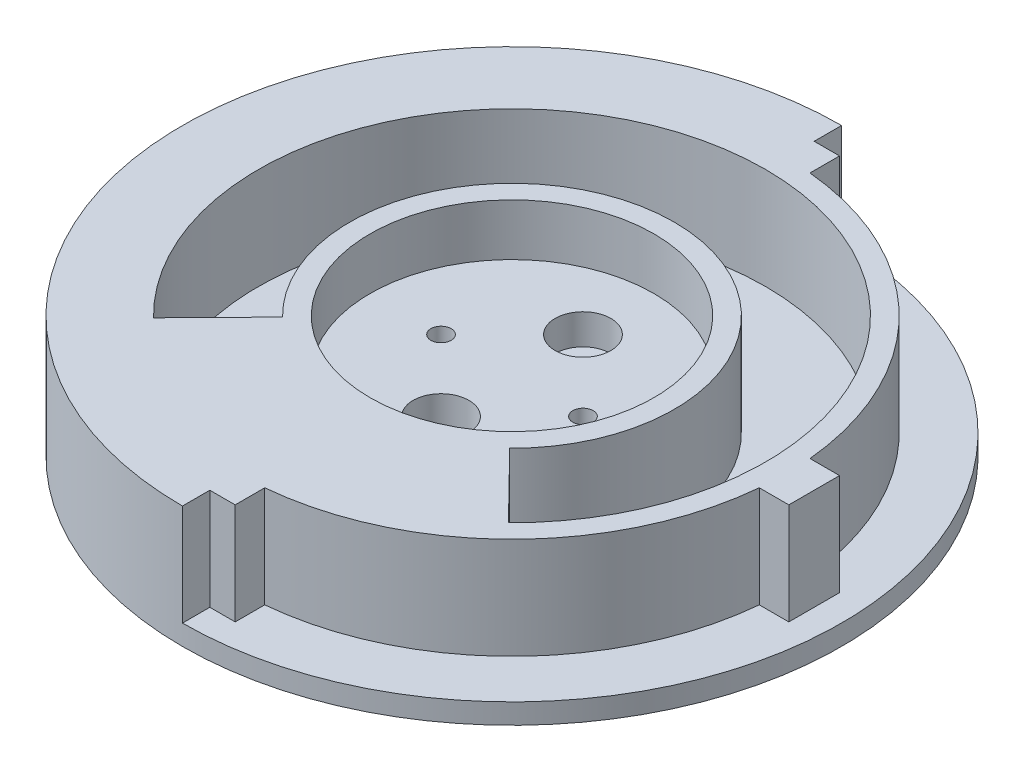
SolidWorks part; units mm, degrees
ref_plane "Front Plane" through (0, 0, 0) normal (0, 0, 1) x (1, 0, 0)
ref_plane "Top Plane" through (0, 0, 0) normal (0, 1, 0) x (1, 0, 0)
ref_plane "Right Plane" through (0, 0, 0) normal (1, 0, 0) x (0, 0, -1)
sketch "Sketch1" plane through (0, 0, 0) normal (0, 1, 0) x (1, 0, 0)
  line L0 (-17.5, -17.8536) -> (-11.2, -11.4263)
  line L1 (0, -55) -> (0, 55) construction
  line L2 (17.5, -17.8536) -> (11.2, -11.4263)
  line L4 (-17.5, -17.8536) -> (3.8221, -38.7535) construction
  circle A0 centre (0, 0) radius 27
  arc A1 (11.2, -11.4263) -> (-11.2, -11.4263) centre (0, 0) ccw
  arc A2 (17.5, -17.8536) -> (-17.5, -17.8536) centre (0, 0) ccw
  circle A3 centre (0, 0) radius 14
  arc A4 (16.5039, 11.7639) -> (14.35, -14.6399) centre (0.1913, -0.1952) cw construction
  circle A5 centre (0, 0) radius 19.9533 construction
  dimension "D1" = 54
  dimension "D2" = 2
  dimension "D3" = 9
  dimension "D4" = 2
  dimension "D5" = 35
extrude "Boss-Extrude1" add sketch "Sketch1" along normal blind 10
sketch "Sketch2" plane through (0, 0, 0) normal (0, -1, 0) x (1, 0, 0)
  circle A0 centre (0, 0) radius 32.5
  circle A1 centre (0, 0) radius 14 construction
  circle A2 centre (0, 0) radius 14 construction
  dimension "D1" = 65
extrude "Boss-Extrude2" add sketch "Sketch2" along normal blind 2
sketch "Sketch3" plane through (0, 0, 0) normal (0, 1, 0) x (1, 0, 0)
  line L0 (0, -5.5) -> (0, 5.5) construction
  line L1 (-2.5, 29.8) -> (2.5, 29.8)
  line L2 (-2.5, 29.8) -> (-2.5, 25.4032)
  line L3 (-2.5, 25.4032) -> (2.5, 25.4032)
  line L4 (2.5, 29.8) -> (2.5, 25.4032)
  line L5 (-2.5, 29.8) -> (2.5, 25.4032) construction
  line L6 (-2.5, 25.4032) -> (2.5, 29.8) construction
  line L7 (29.8, 2.5) -> (25.4032, 2.5)
  line L8 (29.8, 2.5) -> (29.8, -2.5)
  line L9 (29.8, -2.5) -> (25.4032, -2.5)
  line L10 (25.4032, 2.5) -> (25.4032, -2.5)
  line L11 (2.5, -29.8) -> (2.5, -25.4032)
  line L12 (2.5, -29.8) -> (-2.5, -29.8)
  line L13 (-2.5, -29.8) -> (-2.5, -25.4032)
  line L14 (2.5, -25.4032) -> (-2.5, -25.4032)
  line L15 (-29.8, -2.5) -> (-25.4032, -2.5)
  line L16 (-29.8, -2.5) -> (-29.8, 2.5)
  line L17 (-29.8, 2.5) -> (-25.4032, 2.5)
  line L18 (-25.4032, -2.5) -> (-25.4032, 2.5)
  circle A1 centre (0, 0) radius 27 construction
  point P0 (0, 27.6016)
  dimension "D2" = 29.8
  dimension "D1" = 5
  dimension "D3" = 4
extrude "Boss-Extrude3" add sketch "Sketch3" along normal blind 10
sketch "Sketch5" plane through (0, 0, 0) normal (0, 1, 0) x (1, 0, 0)
  line L0 (0, 29.8) -> (0, 32.5)
  line L1 (2.5, 29.8) -> (-2.5, 29.8) construction
  line L2 (0, -6.6) -> (0, 6.6) construction
  line L3 (0, -29.8) -> (0, -32.5)
  line L4 (0, 29.8) -> (-2.5, 29.8)
  line L5 (-2.5, 29.8) -> (-2.5, 26.884)
  line L6 (-26.884, 2.5) -> (-29.8, 2.5)
  line L7 (-29.8, 2.5) -> (-29.8, -2.5)
  line L8 (-29.8, -2.5) -> (-26.884, -2.5)
  line L9 (-2.5, -26.884) -> (-2.5, -29.8)
  line L10 (-2.5, -29.8) -> (0, -29.8)
  line L11 (-2.5, -29.8) -> (2.5, -29.8) construction
  circle A0 centre (0, 0) radius 32.5 construction
  arc A1 (0, 32.5) -> (0, -32.5) centre (0, 0) ccw
  arc A2 (-26.884, 2.5) -> (-2.5, 26.884) centre (0, 0) cw
  arc A3 (-26.884, -2.5) -> (-2.5, -26.884) centre (0, 0) ccw
extrude "Boss-Extrude4" add sketch "Sketch5" along normal up to surface (10 mm away) up to face at (0, 10, 0)
ref_plane "Plane1" through (0, 4.9, 0) normal (0, 1, 0) x (1, 0, 0)
sketch "Sketch6" plane through (0, 4.9, 0) normal (0, 1, 0) x (1, 0, 0)
  circle A0 centre (0, 0) radius 14
extrude "Boss-Extrude5" add sketch "Sketch6" against normal up to surface (4.9 mm away) up to face at (0, 0, 14)
sketch "Sketch4" plane through (0, -2, 0) normal (0, -1, 0) x (1, 0, 0)
  circle A0 centre (0, 0) radius 7 construction
  circle A1 centre (0, -7) radius 1
  circle A2 centre (-7, 0) radius 1
  circle A3 centre (0, 7) radius 1
  circle A4 centre (7, 0) radius 1
  point P14 (0, 0)
  dimension "D1" = 14
  dimension "D2" = 2
  dimension "D3" = 4
extrude "Cut-Extrude1" cut sketch "Sketch4" against normal through all both and the other way through all
sketch "Sketch7" plane through (0, 10, 0) normal (0, 1, 0) x (1, 0, 0)
  line L0 (11.2, -11.4263) -> (17.5, -17.8536) construction
  circle A0 centre (0, 0) radius 20.5 construction
  circle A1 centre (0, -20.5) radius 1.6
  point P5 (14.35, -14.6399)
  dimension "D1" = 3.2
extrude "Cut-Extrude2" [suppressed] cut sketch "Sketch7" against normal through all both and the other way through all
sketch "Sketch8" [suppressed] plane through (0, -2, 0) normal (0, -1, 0) x (1, 0, 0)
  line L0 (6.6, 0) -> (-6.6, 0) construction
  line L1 (-3.1177, 20.5) -> (-1.5588, 17.8)
  line L2 (-1.5588, 17.8) -> (1.5588, 17.8)
  line L3 (1.5588, 17.8) -> (3.1177, 20.5)
  line L4 (3.1177, 20.5) -> (1.5588, 23.2)
  line L5 (1.5588, 23.2) -> (-1.5588, 23.2)
  line L6 (-1.5588, 23.2) -> (-3.1177, 20.5)
  circle A0 centre (0, 20.5) radius 2.7 construction
  dimension "D1" = 5.4
extrude "Cut-Extrude3" [suppressed] cut sketch "Sketch8" against normal blind 4
sketch "Sketch9" [suppressed] plane through (0, 0, 0) normal (1, 0, 0) x (0, 0, -1)
  line L0 (32.5, 10) -> (-32.5, 10) construction
  line L1 (36, -2) -> (30.5, -2)
  line L3 (36, 10) -> (30.5, 10)
  line L4 (30.5, -2) -> (30.5, 10)
  line L5 (32.5, 10) -> (32.5, 0) construction
  arc A0 (36, -2) -> (36, 10) centre (36, 4) ccw
  circle A1 centre (36, 4) radius 1.6
  circle A2 centre (36, 4) radius 3 construction
  dimension "D4" = 3.2
  dimension "D5" = 6
  dimension "D1" = 3.5
  dimension "D2" = 2
  dimension "D3" = 12
extrude "Boss-Extrude6" [suppressed] add sketch "Sketch9" against normal blind 2
mirror "Mirror1" [suppressed] about plane through (0, 0, 0) normal (0, 0, 1)
sketch "Sketch10" plane through (0, 4.9, 0) normal (0, 1, 0) x (1, 0, 0)
  circle A0 centre (0, 7) radius 2.75
  circle A1 centre (0, -7) radius 2.75
  dimension "D1" = 5.5
  dimension "D2" = 5.5
extrude "Cut-Extrude4" cut sketch "Sketch10" against normal blind 3
sketch "Sketch11" plane through (0, -2, 0) normal (0, -1, 0) x (1, 0, 0)
  circle A0 centre (0, 0) radius 4
  dimension "D1" = 8
extrude "Cut-Extrude5" cut sketch "Sketch11" against normal blind 1
